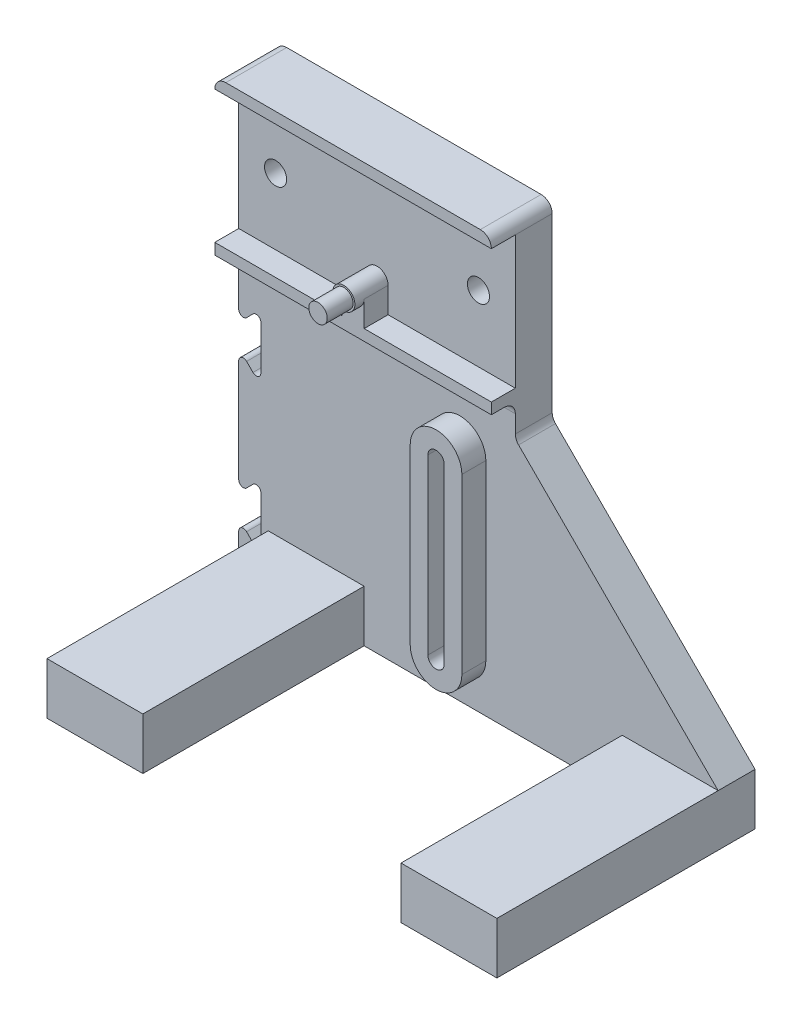
SolidWorks part; units mm, degrees
material "PET"
ref_plane "Front Plane" through (0, 0, 0) normal (0, 0, 1) x (1, 0, 0)
ref_plane "Top Plane" through (0, 0, 0) normal (0, 1, 0) x (1, 0, 0)
ref_plane "Right Plane" through (0, 0, 0) normal (1, 0, 0) x (0, 0, -1)
sketch "Sketch2" plane through (0, 0, 0) normal (0, 0, 1) x (1, 0, 0)
  line L0 (0, 0) -> (130, 0)
  line L1 (130, 0) -> (130, 14)
  line L2 (130, 14) -> (75, 69)
  line L3 (75, 69) -> (75, 120)
  line L4 (75, 120) -> (0, 120)
  line L5 (0, 120) -> (0, 0)
  dimension "D1" = 120
  dimension "D2" = 75
  dimension "D3" = 14
  dimension "D4" = 55
  dimension "D5" = 130
extrude "Boss-Extrude1" add sketch "Sketch2" against normal blind 10
sketch "Sketch3" plane through (0, 0, 0) normal (0, 0, 1) x (1, 0, 0)
  line L0 (75, 69) -> (75, 120) construction
  line L1 (0, 120) -> (75, 120)
  line L2 (0, 120) -> (0, 117)
  line L3 (0, 117) -> (75, 117)
  line L4 (75, 120) -> (75, 117)
  line L5 (0, 120) -> (75, 117) construction
  line L6 (0, 117) -> (75, 120) construction
  line L7 (0, 120) -> (0, 0) construction
  line L8 (0, 81) -> (75, 81)
  line L9 (0, 81) -> (0, 78)
  line L10 (0, 78) -> (75, 78)
  line L11 (75, 81) -> (75, 78)
  line L12 (0, 81) -> (75, 78) construction
  line L13 (0, 78) -> (75, 81) construction
  point P4 (37.5, 118.5)
  point P12 (37.5, 79.5)
  dimension "D1" = 3
  dimension "D2" = 36
extrude "Boss-Extrude2" add sketch "Sketch3" along normal blind 6.5
sketch "Sketch4" plane through (0, 0, 0) normal (0, 0, 1) x (1, 0, 0)
  line L0 (0, 99) -> (75, 99) construction
  line L1 (0, 117) -> (0, 81) construction
  line L2 (75, 81) -> (75, 117) construction
  circle A0 centre (10, 99) radius 3
  circle A1 centre (65, 99) radius 3
  dimension "D1" = 10
  dimension "D3" = 6
  dimension "D2" = 10
extrude "Cut-Extrude2" cut sketch "Sketch4" against normal up to surface (10 mm away) up to face at (68.3333, 53.8333, -10)
sketch "Sketch5" plane through (0, 0, 0) normal (0, 0, 1) x (1, 0, 0)
  line L0 (0, 0) -> (130, 0) construction
  line L1 (130, 14) -> (104, 14)
  line L2 (130, 14) -> (130, 0)
  line L3 (130, 0) -> (104, 0)
  line L4 (104, 14) -> (104, 0)
  line L5 (130, 14) -> (104, 0) construction
  line L6 (130, 0) -> (104, 14) construction
  line L7 (69, 0) -> (69, 120) construction
  line L8 (75, 120) -> (0, 120) construction
  line L9 (8, 0) -> (34, 0)
  line L10 (34, 14) -> (34, 0)
  line L11 (8, 14) -> (34, 14)
  line L12 (8, 14) -> (8, 0)
  line L13 (0, 78) -> (0, 0) construction
  point P4 (117, 7)
  dimension "D1" = 26
  dimension "D2" = 8
extrude "Boss-Extrude3" add sketch "Sketch5" along normal blind 60
sketch "Sketch6" plane through (0, 0, 0) normal (0, 0, 1) x (1, 0, 0)
  line L0 (0, 16) -> (6, 16) construction
  line L1 (0, 78) -> (0, 0) construction
  line L2 (0, 13) -> (6, 7)
  line L3 (6, 7) -> (6, 25)
  line L4 (6, 25) -> (0, 19)
  line L5 (8, 0) -> (34, 0) construction
  line L6 (0, 19) -> (0, 13)
  line L7 (0, 36) -> (-23.6105, 36) construction
  line L8 (0, 56) -> (6, 56) construction
  line L9 (6, 47) -> (0, 53)
  line L10 (6, 65) -> (6, 47)
  line L11 (0, 59) -> (6, 65)
  line L12 (0, 53) -> (0, 59)
  dimension "D1" = 6
  dimension "D2" = 6
  dimension "D3" = 16
  dimension "D4" = 6
  dimension "D5" = 40
sketch "Sketch7" plane through (0, 0, 0) normal (0, 0, 1) x (1, 0, 0)
  line L0 (60, 0) -> (60, 120) construction
  line L1 (34, 0) -> (104, 0) construction
  line L2 (75, 120) -> (0, 120) construction
  line L3 (60, 13) -> (60, 60) construction
  line L4 (53, 13) -> (53, 60)
  line L5 (67, 13) -> (67, 60)
  arc A0 (53, 13) -> (67, 13) centre (60, 13) ccw
  arc A1 (67, 60) -> (53, 60) centre (60, 60) ccw
  point P4 (60, 36.5)
  point P14 (60, 6)
  point P15 (60, 67)
  dimension "D1" = 26
  dimension "D2" = 7
  dimension "D3" = 6
extrude "Boss-Extrude5" add sketch "Sketch7" along normal up to surface (6.5 mm away) up to face at (37.5, 79.5, 6.5)
sketch "Sketch8" plane through (0, 0, 6.5) normal (0, 0, 1) x (1, 0, 0)
  line L4 (62.2, 13) -> (62.2, 60)
  line L5 (57.8, 60) -> (57.8, 13)
  line L6 (62.2, 13) -> (62.2, 60)
  line L7 (57.8, 60) -> (57.8, 13)
  arc A4 (57.8, 13) -> (62.2, 13) centre (60, 13) ccw
  arc A5 (62.2, 60) -> (57.8, 60) centre (60, 60) ccw
  arc A6 (57.8, 13) -> (62.2, 13) centre (60, 13) ccw
  arc A7 (62.2, 60) -> (57.8, 60) centre (60, 60) ccw
  dimension "D1" = 4.8
extrude "Cut-Extrude3" cut sketch "Sketch8" against normal through all
fillet "Fillet2" radius 3 4 edges at (75, 120, -1.75) (0, 120, -1.75) (37.5, 78, 0) (75, 69, -5)
extrude "Cut-Extrude4" cut sketch "Sketch6" against normal through all
fillet "Fillet3" radius 1.25 8 edges at (6, 25, -5) (6, 7, -5) (0, 13, -5) (0, 19, -5) (6, 47, -5) (0, 53, -5) (6, 65, -5) (0, 59, -5)
sketch "Sketch9" plane through (0, 0, 0) normal (0, 0, 1) x (1, 0, 0)
  line L0 (75, 78) -> (0, 78) construction
  line L1 (0, 78) -> (75, 78) construction
  line L2 (0, 117) -> (0, 62.0178) construction
  line L3 (75, 70.2426) -> (75, 117) construction
  circle A0 centre (37.5, 87.9) radius 2.5
  point P0 (37.5, 87.9)
  point P13 (37.5, 78)
  dimension "D2" = 5
  dimension "D1" = 9.9
extrude "Boss-Extrude6" add sketch "Sketch9" along normal blind 16
sketch "Sketch10" plane through (0, 0, -10) normal (0, 0, -1) x (-1, 0, 0)
  line L4 (-56, 13) -> (-56, 60)
  line L5 (-64, 60) -> (-64, 13)
  line L6 (-56, 13) -> (-56, 60)
  line L7 (-64, 60) -> (-64, 13)
  arc A4 (-64, 13) -> (-56, 13) centre (-60, 13) ccw
  arc A5 (-56, 60) -> (-64, 60) centre (-60, 60) ccw
  arc A6 (-64, 13) -> (-56, 13) centre (-60, 13) ccw
  arc A7 (-56, 60) -> (-64, 60) centre (-60, 60) ccw
  dimension "D1" = 1.8
extrude "Cut-Extrude5" cut sketch "Sketch10" against normal blind 4
sketch "Sketch11" plane through (0, 0, 0) normal (0, 0, 1) x (1, 0, 0)
  line L0 (34.5, 87.9) -> (34.5, 81)
  line L1 (75, 81) -> (0, 81) construction
  line L2 (34.5, 81) -> (40.5, 81)
  line L3 (40.5, 81) -> (40.5, 87.9)
  circle A5 centre (37.5, 87.9) radius 3
  circle A7 centre (37.5, 87.9) radius 2.5 construction
  point P8 (30.1841, 89.6401)
  circle M3 centre (37.5, 87.9) radius 2.5
  line M7 (0, 81) -> (75, 81)
  dimension "D1" = 6
extrude "Boss-Extrude7" add sketch "Sketch11" along normal up to surface (6.5 mm away) contours L3 L0 M7 M3 | A5 region at (37.5, 83.3212, 0) up to face at (37.5, 79.5, 6.5)
sketch "Sketch12" plane through (0, 0, 6.5) normal (0, 0, 1) x (1, 0, 0)
  circle A0 centre (37.5, 87.9) radius 3
  arc A1 (40.5, 87.9) -> (34.5, 87.9) centre (37.5, 87.9) ccw construction
extrude "Boss-Extrude8" add sketch "Sketch12" along normal blind 2.5
